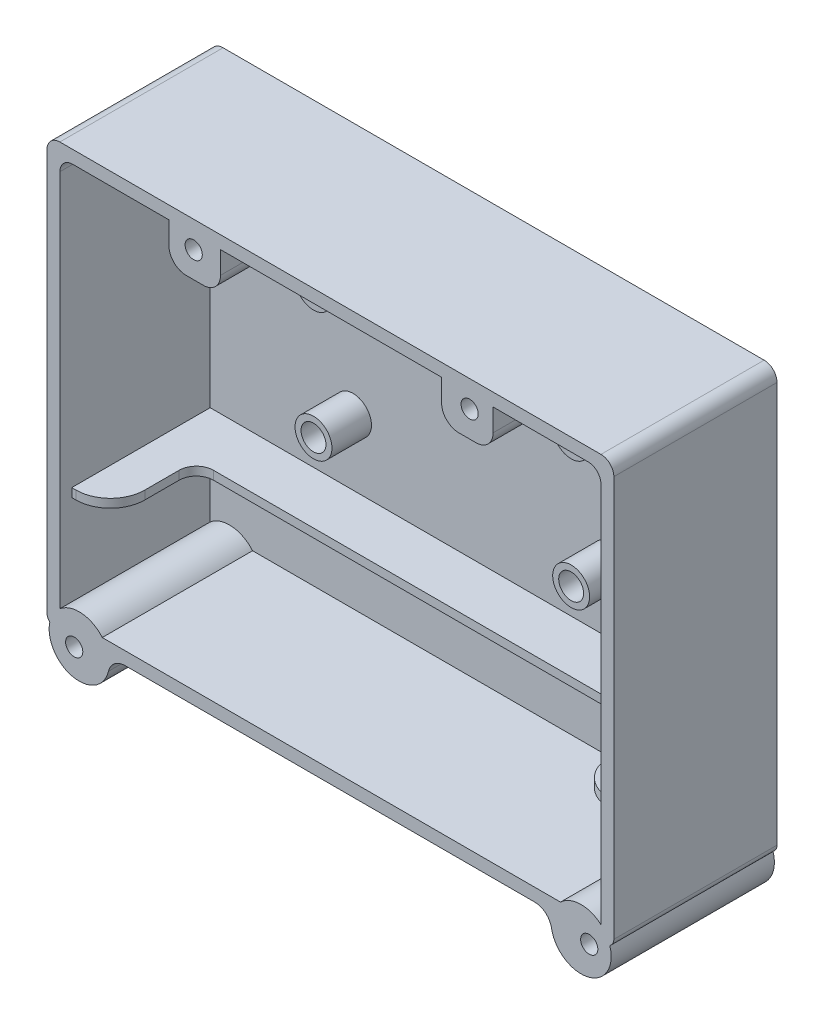
SolidWorks part; units mm, degrees
ref_plane "Front Plane" through (0, 0, 0) normal (0, 0, 1) x (1, 0, 0)
ref_plane "Top Plane" through (0, 0, 0) normal (0, 1, 0) x (1, 0, 0)
ref_plane "Right Plane" through (0, 0, 0) normal (1, 0, 0) x (0, 0, -1)
other "Graphic1"
ref_plane "Plane1" through (0, 0, 30) normal (0, 0, 1) x (1, 0, 0)
sketch "Sketch1" plane through (0, 0, 30) normal (0, 0, 1) x (1, 0, 0)
  line L1 (72.8096, 320.0447) -> (138.8096, 320.0447)
  line L2 (72.8096, 320.0447) -> (72.8096, 271.0447)
  line L3 (72.8096, 271.0447) -> (138.8096, 271.0447)
  line L4 (138.8096, 320.0447) -> (138.8096, 271.0447)
  dimension "D1" = 66
  dimension "D2" = 49
extrude "Boss-Extrude1" add sketch "Sketch1" along normal blind 19
shell "Shell1" thickness 1.5 removed face at (105.8096, 295.5447, 49)
sketch "Sketch2" plane through (0, 0, 31.5) normal (0, 0, 1) x (1, 0, 0)
  line L0 (137.3096, 318.5447) -> (74.3096, 318.5447) construction
  line L1 (87.0113, 318.5447) -> (93.0113, 318.5447)
  line L3 (87.0113, 313.9447) -> (93.0113, 313.9447)
  line L4 (93.0113, 318.5447) -> (93.0113, 313.9447)
  line L5 (87.0113, 318.5447) -> (87.0113, 313.9447)
  line L6 (118.7567, 318.5447) -> (124.7567, 318.5447)
  line L7 (118.7567, 318.5447) -> (118.7567, 313.9447)
  line L8 (118.7567, 313.9447) -> (124.7567, 313.9447)
  line L9 (124.7567, 318.5447) -> (124.7567, 313.9447)
  dimension "D1" = 6
  dimension "D2" = 4.6
extrude "Boss-Extrude2" add sketch "Sketch2" along normal up to surface (17.5 mm away) up to face at (105.8096, 295.5447, 49)
fillet "Fillet1" radius 1.5 4 edges at (137.3096, 318.5447, 40.25) (74.3096, 318.5447, 40.25) (72.8096, 320.0447, 39.5) (138.8096, 320.0447, 39.5)
sketch "Sketch3" plane through (0, 0, 31.5) normal (0, 0, 1) x (1, 0, 0)
  circle A0 centre (90.9398, 307.1114) radius 1.45
  circle A1 centre (90.9398, 307.1114) radius 2.15
  circle A5 centre (120.9398, 307.1114) radius 2.15
  circle A6 centre (120.9398, 307.1114) radius 1.45
  circle A7 centre (120.9398, 292.1114) radius 2.15
  circle A8 centre (120.9398, 292.1114) radius 1.45
  circle A9 centre (90.9398, 292.1114) radius 2.15
  circle A10 centre (90.9398, 292.1114) radius 1.45
  dimension "D1" = 2
  dimension "D2" = 2
extrude "Boss-Extrude3" add sketch "Sketch3" along normal blind 4.6
ref_plane "Plane2" through (0, 284, 0) normal (0, 1, 0) x (1, 0, 0)
sketch "Sketch4" plane through (0, 284, 0) normal (0, 1, 0) x (1, 0, 0)
  line L0 (72.8096, -47.6156) -> (78.8096, -47.6156)
  line L1 (72.8096, -49) -> (72.8096, -30) construction
  line L2 (78.8096, -47.6156) -> (78.8096, -37.6156)
  line L3 (78.8096, -37.6156) -> (132.8096, -37.6156)
  line L4 (132.8096, -37.6156) -> (132.8096, -47.6156)
  line L5 (132.8096, -47.6156) -> (138.8096, -47.6156)
  line L6 (138.8096, -49) -> (138.8096, -30) construction
  line L7 (138.8096, -47.6156) -> (138.8096, -30)
  line L8 (-39.0934, -30) -> (39.0934, -30) construction
  line L9 (138.8096, -30) -> (72.8096, -30)
  line L10 (72.8096, -30) -> (72.8096, -47.6156)
  dimension "D1" = 6
extrude "Boss-Extrude4" add sketch "Sketch4" along normal mid plane 1
fillet "Fillet2" radius 4 2 edges at (78.8096, 284, 47.6156) (132.8096, 284, 47.6156)
fillet "Fillet3" radius 2 2 edges at (132.8096, 284, 37.6156) (78.8096, 284, 37.6156)
sketch "Sketch5" plane through (0, 0, 49) normal (0, 0, 1) x (1, 0, 0)
  circle A0 centre (76.561, 270.2994) radius 3.5
  circle A1 centre (135, 270) radius 3.5
  dimension "D1" = 7
extrude "Boss-Extrude5" add sketch "Sketch5" against normal up to surface (19 mm away) up to face at (105.8096, 303.3149, 30)
fillet "Fillet4" radius 2 6 edges at (131.6595, 271.0447, 39.5) (79.9808, 271.0447, 39.5) (124.7567, 313.9447, 40.25) (118.7567, 313.9447, 40.25) (87.0113, 313.9447, 40.25) (93.0113, 313.9447, 40.25)
sketch "Sketch6" plane through (0, 0, 49) normal (0, 0, 1) x (1, 0, 0)
  circle A0 centre (89.8921, 316.9681) radius 1
  circle A1 centre (122.0225, 316.9681) radius 1
  circle A2 centre (75.9788, 269.9633) radius 1
  circle A3 centre (135.944, 269.9633) radius 1
extrude "Cut-Extrude1" cut sketch "Sketch6" against normal through all
fillet "Fillet5" radius 1 2 edges at (72.8096, 271.0447, 39.5) (138.8096, 271.0447, 39.5)
